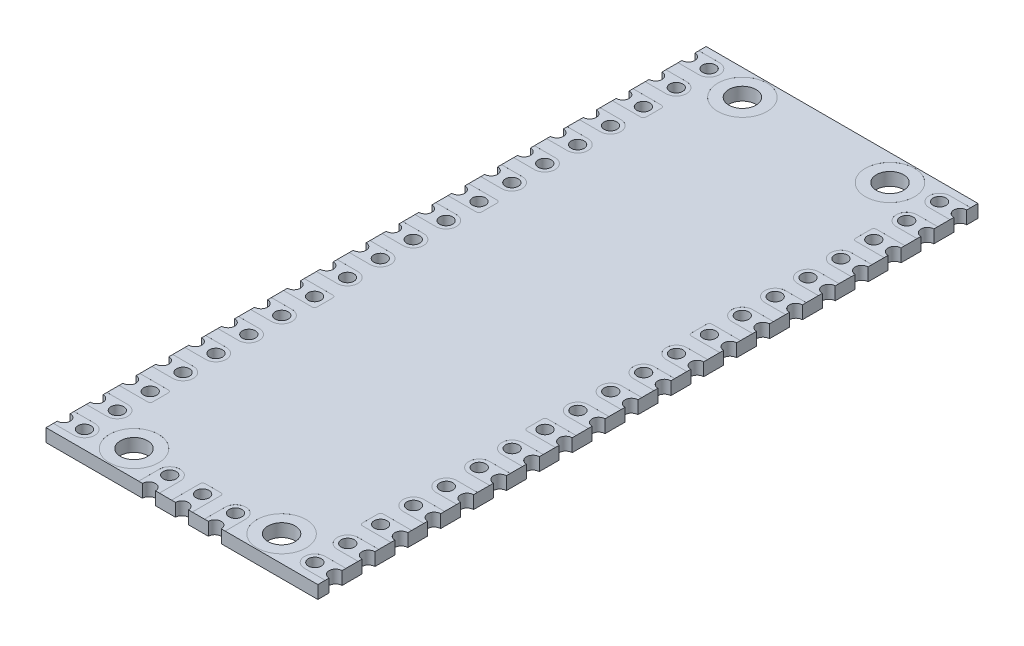
SolidWorks part; units mm, degrees
material "Power Circuit Board"
ref_plane "Front Plane" through (0, 0, 0) normal (0, 0, 1) x (1, 0, 0)
ref_plane "Top Plane" through (0, 0, 0) normal (0, 1, 0) x (1, 0, 0)
ref_plane "Right Plane" through (0, 0, 0) normal (1, 0, 0) x (0, 0, -1)
sketch "BaseS" plane through (0, 0, 0) normal (0, 1, 0) x (1, 0, 0)
  line L1 (-10.5, 25.5) -> (10.5, 25.5)
  line L2 (-10.5, 25.5) -> (-10.5, -25.5)
  line L3 (-10.5, -25.5) -> (10.5, -25.5)
  line L4 (10.5, 25.5) -> (10.5, -25.5)
  line L5 (-10.5, 25.5) -> (10.5, -25.5) construction
  line L6 (-10.5, -25.5) -> (10.5, 25.5) construction
  point P0 (0, 0)
  dimension "Width" = 21
  dimension "Length" = 51
extrude "Base" add sketch "BaseS" against normal mid plane 1
hole_wizard "Ø1.0 (1) Diameter Hole1" positions "Sketch2" profile "Sketch3" hole size "Ø1.0" standard "ANSI Metric" end condition through all
sketch "Sketch2" plane through (0, 0.5, 0) normal (0, 1, 0) x (1, 0, 0)
  line L0 (-10.5, 25.5) -> (-10.5, -25.5) construction
  line L1 (-10.5, -25.5) -> (10.5, -25.5) construction
  point P0 (-8.9, -24.13)
  dimension "XDim" = 1.6
  dimension "YDim" = 1.37
sketch "Sketch3" plane through (-8.9, 0.5, 24.13) normal (1, 0, 0) x (0, 0, 1)
  line L0 (0, 0) -> (0, 1)
  line L1 (0, 1) -> (0.5, 1)
  line L2 (0.5, 1) -> (0.5, 0)
  line L5 (0.5, 0) -> (0, 0)
  line L11 (0, -6.35) -> (0, 107.95) construction
  dimension "Thru Hole Dia." = 1
  dimension "Thru Hole Depth" = 1
pattern_linear "HoleHorzLP" count 2 spacing 1.6 along (-1, 0, 0) of "Ø1.0 (1) Diameter Hole1"
sketch "SlotCutS" plane through (0, 0.5, 0) normal (0, 1, 0) x (1, 0, 0)
  line L0 (-8.9, -24.13) -> (-10.5, -24.13) construction
  line L1 (-8.9, -24.93) -> (-10.5, -24.93)
  line L2 (-8.9, -23.33) -> (-10.5, -23.33)
  arc A0 (-8.9, -24.93) -> (-8.9, -23.33) centre (-8.9, -24.13) ccw
  arc A1 (-10.5, -23.33) -> (-10.5, -24.93) centre (-10.5, -24.13) ccw
  circle A2 centre (-8.9, -24.13) radius 0.5 construction
  point P4 (-9.7, -24.13)
  dimension "RefDia" = 0.8
  dimension "DiaControl" = 0.3
extrude "SlotCut" cut sketch "SlotCutS" against normal blind 0.001
pattern_linear "HoleHorzLPSlotLP" count 20 spacing 2.54 along (0, 0, -1) of "Ø1.0 (1) Diameter Hole1", "HoleHorzLP", "SlotCut"
mirror "SHLPHM" about plane through (0, 0, 0) normal (1, 0, 0) of "Ø1.0 (1) Diameter Hole1", "HoleHorzLPSlotLP", "HoleHorzLP", "SlotCut"
hole_wizard "Ø2.1 (2.1) Diameter Hole1" positions "Sketch5" profile "Sketch6" hole size "Ø2.1" standard "ANSI Metric" end condition through all
sketch "Sketch5" plane through (0, 0.5, 0) normal (0, 1, 0) x (1, 0, 0)
  line L0 (-10.5, -25.5) -> (10.5, -25.5) construction
  line L1 (-10.5, -24.93) -> (-10.5, -25.5) construction
  point P0 (-5.7, -23.5)
  dimension "YDim" = 2
  dimension "XDim" = 4.8
sketch "Sketch6" plane through (-5.7, 0.5, 23.5) normal (1, 0, 0) x (0, 0, 1)
  line L0 (0, 0) -> (0, 1)
  line L1 (0, 1) -> (1.05, 1)
  line L2 (1.05, 1) -> (1.05, 0)
  line L5 (1.05, 0) -> (0, 0)
  line L11 (0, -6.35) -> (0, 107.95) construction
  dimension "Thru Hole Dia." = 2.1
  dimension "Thru Hole Depth" = 1
sketch "Soldering2.1mmHoleCutoutS" plane through (0, 0.5, 0) normal (0, 1, 0) x (1, 0, 0)
  circle A0 centre (-5.7, -23.5) radius 1.9
  circle A1 centre (-5.7, -23.5) radius 1.05 construction
  dimension "RefDia" = 3.8
  dimension "DiaControl" = 0.85
extrude "Soldering2.1mmHoleCutout" cut sketch "Soldering2.1mmHoleCutoutS" against normal up to surface (0.001 mm away) up to face at (-9.75, 0.499, 24.13)
mirror "SHCHM" about plane through (0, 0, 0) normal (1, 0, 0) of "Ø2.1 (2.1) Diameter Hole1", "Soldering2.1mmHoleCutout"
mirror "SHCHMVM" about plane through (0, 0, 0) normal (0, 0, 1) of "SHCHM", "Soldering2.1mmHoleCutout", "Ø2.1 (2.1) Diameter Hole1"
mirror "SHCTopVM" about plane through (0, 0, 0) normal (0, 1, 0) of "SHCHMVM", "SHCHM", "Soldering2.1mmHoleCutout"
sketch "SquareEtchS" plane through (0, 0.5, 0) normal (0, 1, 0) x (1, 0, 0)
  line L0 (-10.5, -19.85) -> (-10.5, -20.79) construction
  line L1 (-10.5, -18.25) -> (-8.3, -18.25)
  line L2 (-10.5, -18.25) -> (-10.5, -19.85)
  line L3 (-10.5, -19.85) -> (-8.3, -19.85)
  line L4 (-8.1, -18.45) -> (-8.1, -19.65)
  line L5 (-10.5, -19.85) -> (-8.9, -19.85) construction
  arc A0 (-8.9, -19.85) -> (-8.9, -18.25) centre (-8.9, -19.05) ccw construction
  arc A1 (-8.3, -19.85) -> (-8.1, -19.65) centre (-8.3, -19.65) ccw
  arc A2 (-8.1, -18.45) -> (-8.3, -18.25) centre (-8.3, -18.45) ccw
  dimension "Radius" = 0.2
extrude "SquareEtch" cut sketch "SquareEtchS" against normal up to surface (0.001 mm away) up to face at (-9.75, 0.499, 19.05)
pattern_linear "SELP" count 4 spacing 12.7 along (0, 0, -1) of "SquareEtch"
mirror "SELPHM" about plane through (0, 0, 0) normal (1, 0, 0) of "SELP", "SquareEtch"
hole_wizard "Ø1.0 (1) Diameter Hole2" positions "Sketch9" profile "Sketch10" hole size "Ø1.0" standard "ANSI Metric" end condition through all
sketch "Sketch9" plane through (0, 0.5, 0) normal (0, 1, 0) x (1, 0, 0)
  line L0 (0, -25.5) -> (0, -23.9) construction
  line L1 (-10.5, -25.5) -> (10.5, -25.5) construction
  point P0 (0, -23.9)
  dimension "YDim" = 1.6
sketch "Sketch10" plane through (0, 0.5, 23.9) normal (1, 0, 0) x (0, 0, 1)
  line L0 (0, 0) -> (0, 1)
  line L1 (0, 1) -> (0.5, 1)
  line L2 (0.5, 1) -> (0.5, 0)
  line L5 (0.5, 0) -> (0, 0)
  line L11 (0, -6.35) -> (0, 107.95) construction
  dimension "Thru Hole Dia." = 1
  dimension "Thru Hole Depth" = 1
sketch "VerticalSlotCutS" plane through (0, 0.5, 0) normal (0, 1, 0) x (1, 0, 0)
  line L0 (0, -23.9) -> (0, -25.5) construction
  line L1 (-10.5, -25.5) -> (10.5, -25.5) construction
  line L2 (0.8, -23.9) -> (0.8, -25.5)
  line L3 (-0.8, -23.9) -> (-0.8, -25.5)
  line L4 (-8.9, -24.13) -> (-10.5, -24.13) construction
  arc A0 (0.8, -23.9) -> (-0.8, -23.9) centre (0, -23.9) ccw
  arc A1 (-0.8, -25.5) -> (0.8, -25.5) centre (0, -25.5) ccw
  arc A2 (-8.9, -24.93) -> (-8.9, -23.33) centre (-8.9, -24.13) ccw construction
  point P4 (0, -24.7)
extrude "VerticalSlotCut" cut sketch "VerticalSlotCutS" against normal up to surface (0.999 mm away)
pattern_linear "DH2LP" count 2 spacing 1.6 along (0, 0, 1) of "Ø1.0 (1) Diameter Hole2"
pattern_linear "VSCHLP" count 2 spacing 2.54 along (1, 0, 0) count 2 spacing 2.54 along (-1, 0, 0) of "VerticalSlotCut", "Ø1.0 (1) Diameter Hole2", "DH2LP"
sketch "VerticalSquareEtchS" plane through (0, 0.5, 0) normal (0, 1, 0) x (1, 0, 0)
  line L0 (-1.74, -25.5) -> (-0.8, -25.5) construction
  line L1 (-0.6, -23.1) -> (0.6, -23.1)
  line L2 (-0.8, -23.3) -> (-0.8, -25.5)
  line L3 (-0.8, -25.5) -> (0.8, -25.5)
  line L4 (0.8, -23.3) -> (0.8, -25.5)
  line L5 (-0.8, -23.9) -> (-0.8, -25.5) construction
  arc A0 (0.8, -23.9) -> (-0.8, -23.9) centre (0, -23.9) ccw construction
  arc A1 (0.8, -23.3) -> (0.6, -23.1) centre (0.6, -23.3) ccw
  arc A2 (-0.6, -23.1) -> (-0.8, -23.3) centre (-0.6, -23.3) ccw
  arc A3 (-8.3, -19.85) -> (-8.1, -19.65) centre (-8.3, -19.65) ccw construction
extrude "VerticalSquareEtch" cut sketch "VerticalSquareEtchS" against normal up to surface (0.001 mm away)
sketch "VSCHPVMS" plane through (0, -0.5, 0) normal (0, -1, 0) x (1, 0, 0)
  line L0 (3.04, 25.5) -> (3.34, 25.5) construction
  line L1 (3.34, 25.5) -> (3.34, 23.9) construction
  line L2 (1.74, 23.9) -> (1.74, 25.5) construction
  line L3 (1.74, 25.5) -> (2.04, 25.5) construction
  line L4 (-2.04, 25.5) -> (-1.74, 25.5) construction
  line L5 (-1.74, 25.5) -> (-1.74, 23.9) construction
  line L6 (-3.34, 23.9) -> (-3.34, 25.5) construction
  line L7 (-3.34, 25.5) -> (-3.04, 25.5) construction
  line L8 (0.5, 25.5) -> (0.8, 25.5) construction
  line L9 (0.8, 25.5) -> (0.8, 23.3) construction
  line L10 (0.6, 23.1) -> (-0.6, 23.1) construction
  line L11 (-0.8, 23.3) -> (-0.8, 25.5) construction
  line L12 (-0.8, 25.5) -> (-0.5, 25.5) construction
  line L13 (3.04, 25.5) -> (3.34, 25.5)
  line L14 (3.34, 25.5) -> (3.34, 23.9)
  line L15 (1.74, 23.9) -> (1.74, 25.5)
  line L16 (1.74, 25.5) -> (2.04, 25.5)
  line L17 (-2.04, 25.5) -> (-1.74, 25.5)
  line L18 (-1.74, 25.5) -> (-1.74, 23.9)
  line L19 (-3.34, 23.9) -> (-3.34, 25.5)
  line L20 (-3.34, 25.5) -> (-3.04, 25.5)
  line L21 (0.5, 25.5) -> (0.8, 25.5)
  line L22 (0.8, 25.5) -> (0.8, 23.3)
  line L23 (0.6, 23.1) -> (-0.6, 23.1)
  line L24 (-0.8, 23.3) -> (-0.8, 25.5)
  line L25 (-0.8, 25.5) -> (-0.5, 25.5)
  arc A0 (2.04, 25.5) -> (3.04, 25.5) centre (2.54, 25.5) ccw construction
  arc A1 (1.74, 23.9) -> (3.34, 23.9) centre (2.54, 23.9) ccw construction
  arc A2 (-3.04, 25.5) -> (-2.04, 25.5) centre (-2.54, 25.5) ccw construction
  arc A3 (-3.34, 23.9) -> (-1.74, 23.9) centre (-2.54, 23.9) ccw construction
  arc A4 (-0.5, 25.5) -> (0.5, 25.5) centre (0, 25.5) ccw construction
  arc A5 (0.6, 23.1) -> (0.8, 23.3) centre (0.6, 23.3) ccw construction
  arc A6 (-0.8, 23.3) -> (-0.6, 23.1) centre (-0.6, 23.3) ccw construction
  arc A7 (2.04, 25.5) -> (3.04, 25.5) centre (2.54, 25.5) ccw
  arc A8 (1.74, 23.9) -> (3.34, 23.9) centre (2.54, 23.9) ccw
  arc A9 (-3.04, 25.5) -> (-2.04, 25.5) centre (-2.54, 25.5) ccw
  arc A10 (-3.34, 23.9) -> (-1.74, 23.9) centre (-2.54, 23.9) ccw
  arc A11 (-0.5, 25.5) -> (0.5, 25.5) centre (0, 25.5) ccw
  arc A12 (0.6, 23.1) -> (0.8, 23.3) centre (0.6, 23.3) ccw
  arc A13 (-0.8, 23.3) -> (-0.6, 23.1) centre (-0.6, 23.3) ccw
extrude "VSCHPVM" cut sketch "VSCHPVMS" against normal blind 0.001
equation "\"Depth@VSCHPVM\"=\"Depth@SlotCut\""
